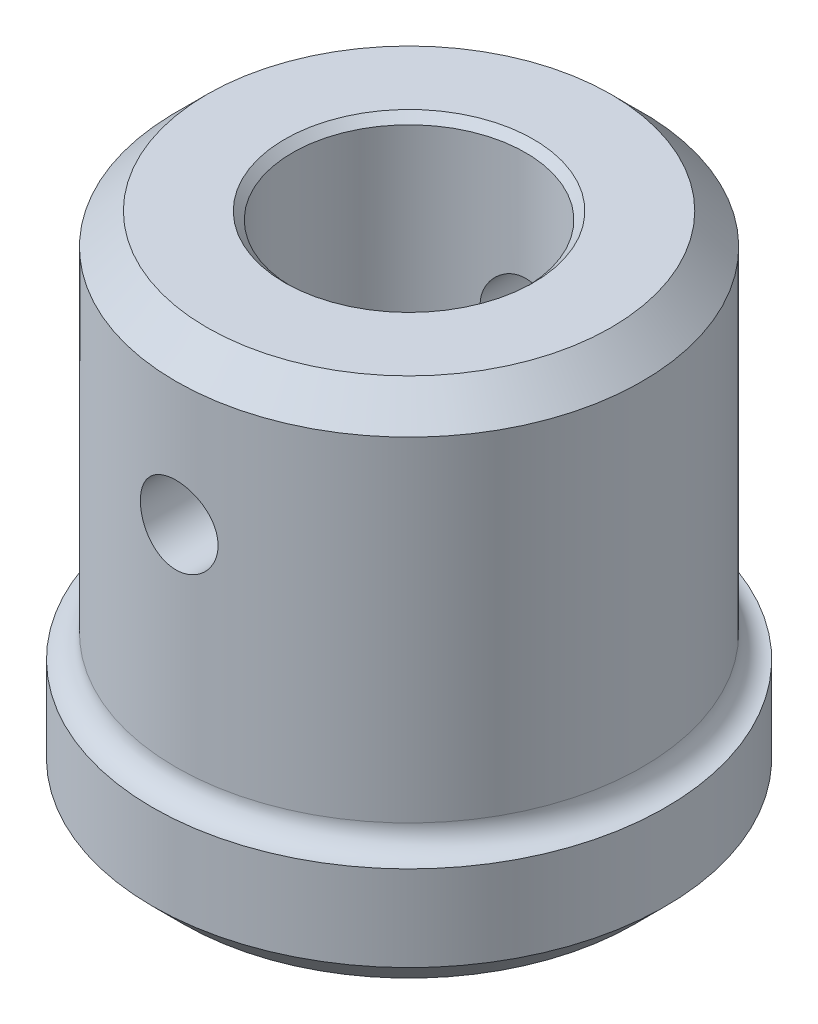
SolidWorks part; units mm, degrees
material "1.0060 (E335)"
ref_plane "Front Plane" through (0, 0, 0) normal (0, 0, 1) x (1, 0, 0)
ref_plane "Top Plane" through (0, 0, 0) normal (0, 1, 0) x (1, 0, 0)
ref_plane "Right Plane" through (0, 0, 0) normal (1, 0, 0) x (0, 0, -1)
sketch "Sketch1" plane through (0, 0, 0) normal (0, 1, 0) x (1, 0, 0)
  circle A0 centre (0, 0) radius 33
  dimension "D1" = 66
extrude "Boss-Extrude1" add sketch "Sketch1" along normal blind 15
sketch "Sketch2" plane through (0, 15, 0) normal (0, 1, 0) x (1, 0, 0)
  circle A0 centre (0, 0) radius 30
  dimension "D1" = 60
extrude "Boss-Extrude2" add sketch "Sketch2" along normal blind 50
fillet "Fillet1" radius 3 1 edges at (0, 15, 30)
sketch "Sketch3" plane through (0, 65, 0) normal (0, 1, 0) x (1, 0, 0)
  circle A0 centre (0, 0) radius 15
  dimension "D1" = 30
extrude "Cut-Extrude1" cut sketch "Sketch3" against normal blind 50
chamfer "Chamfer1" distance 1 angle 45 1 edges at (0, 65, 15)
chamfer "Chamfer2" distance 4 angle 45 2 edges at (0, 65, 30) (0, 0, 33)
sketch "Sketch4" plane through (0, 0, 0) normal (0, 0, 1) x (1, 0, 0)
  line L0 (0, -1000) -> (0, 49000) construction
  line L1 (0, 15) -> (0, 17)
  line L2 (-16, 15) -> (0, 15)
  line L4 (33, 15) -> (-33, 15) construction
  line L5 (-16, 15) -> (-16, 17)
  line L6 (-16, 17) -> (0, 17)
  point P4 (0, 0)
  point P5 (0, 13.2461)
  point P9 (0, 13.827)
  dimension "D1" = 2
  dimension "D2" = 32
revolve "Cut-Revolve1" cut sketch "Sketch4" angle 360 about L0
fillet "Fillet2" radius 1 2 edges at (16, 17, 0) (16, 15, 0)
sketch "Sketch5" plane through (0, 0, 0) normal (0, 0, 1) x (1, 0, 0)
  line L0 (26, 65) -> (-26, 65) construction
  circle A0 centre (0, 45) radius 5
  point P2 (0, 0)
  dimension "D1" = 10
  dimension "D2" = 20
extrude "Cut-Extrude2" cut sketch "Sketch5" against normal through all both and the other way through all
